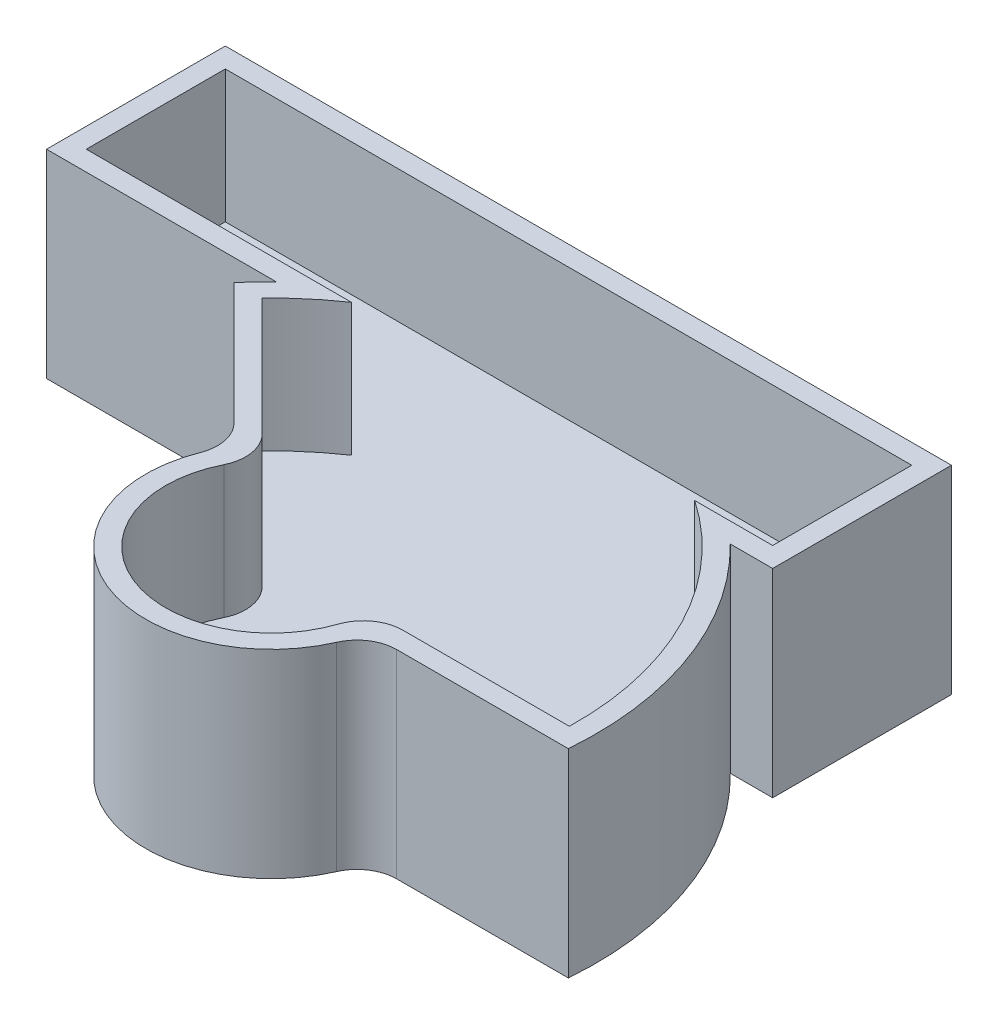
SolidWorks part; units mm, degrees
ref_plane "Alzado" through (0, 0, 0) normal (0, 0, 1) x (1, 0, 0)
ref_plane "Planta" through (0, 0, 0) normal (0, 1, 0) x (1, 0, 0)
ref_plane "Vista lateral" through (0, 0, 0) normal (1, 0, 0) x (0, 0, -1)
sketch "Croquis1" plane through (0, 0, 0) normal (0, 1, 0) x (1, 0, 0)
  line L0 (-35, 32.5) -> (35, -32.5) construction
  line L1 (-35, 32.5) -> (35, 32.5)
  line L2 (-35, 32.5) -> (-35, -32.5)
  line L3 (-35, -32.5) -> (35, -32.5)
  line L4 (35, 32.5) -> (35, -32.5)
  dimension "D1" = 70
  dimension "D2" = 65
extrude "Extruir1" add sketch "Croquis1" along normal blind 5
sketch "Croquis2" plane through (0, 5, 0) normal (0, 1, 0) x (1, 0, 0)
  line L0 (0, 32.5) -> (0, -32.5) construction
  line L1 (35, 32.5) -> (-35, 32.5) construction
  line L2 (-35, -32.5) -> (35, -32.5) construction
  circle A0 centre (0, -17.5) radius 4
  dimension "D1" = 8
  dimension "D2" = 15
extrude "Extruir2" cut sketch "Croquis2" against normal blind 5
sketch "Croquis3" plane through (0, 5, 0) normal (0, 1, 0) x (1, 0, 0)
  line L0 (0, -32.5) -> (0, 32.5) construction
  line L1 (-35, -32.5) -> (35, -32.5) construction
  line L2 (35, 32.5) -> (-35, 32.5) construction
  line L3 (-32.9868, -32.5) -> (-32.9868, 32.5) construction
  line L4 (-32.9868, 1.5) -> (-12.9615, 1.5)
  line L5 (18.8496, -32.5) -> (18.8496, 32.5) construction
  line L6 (-32.9868, 3.5) -> (18.8496, 3.5) construction
  line L7 (-32.9868, 2) -> (0, 2) construction
  line L8 (-32.9868, 11.5) -> (18.8496, 11.5) construction
  line L9 (0, -17.5) -> (-14.8492, -2.6508) construction
  line L10 (0, -17.5) -> (14.8492, -2.6508) construction
  line L11 (0, 2) -> (18.8496, 2) construction
  line L12 (-32.9868, 2) -> (18.8496, 2) construction
  line L13 (-32.9868, 12) -> (18.8496, 12)
  line L14 (-5.3033, -12.1967) -> (-16.2635, -1.2365) construction
  line L15 (12.9615, 1.5) -> (18.8496, 1.5)
  line L16 (-32.9868, 1.5) -> (18.8496, 1.5) construction
  line L17 (7.9844, -18) -> (22.9946, -18)
  line L18 (-5.9993, -12.2078) -> (-16.6132, -1.5939)
  line L19 (0, -17.5) -> (23, -17.5) construction
  line L20 (7.5, -17.5) -> (23, -17.5) construction
  line L21 (-5.6569, -12.5503) -> (-16.617, -1.5901) construction
  line L22 (7.5, -18) -> (23, -18) construction
  line L23 (-32.9868, 12) -> (-32.9868, 1.5)
  line L24 (18.8496, 12) -> (18.8496, 1.5)
  line L25 (-34.4868, 13.5) -> (20.3496, 13.5)
  line L26 (20.3496, 13.5) -> (20.3496, 0)
  line L27 (17.1464, 0) -> (20.3496, 0)
  line L28 (9.2871, -19.5) -> (24.4182, -19.5)
  line L29 (-7.9812, -12.3473) -> (-18.6805, -1.6479)
  line L30 (-34.4868, 0) -> (-17.1464, 0)
  line L31 (-34.4868, 13.5) -> (-34.4868, 0)
  circle A0 centre (0, -17.5) radius 21 construction
  circle A1 centre (0, -17.5) radius 7.5 construction
  arc A2 (-12.9615, 1.5) -> (-16.6132, -1.5939) centre (0, -17.5) ccw
  circle A3 centre (0, -17.5) radius 23 construction
  arc A4 (-5.9993, -12.2078) -> (7.9844, -18) centre (0, -17.5) ccw
  arc A5 (22.9946, -18) -> (12.9615, 1.5) centre (0, -17.5) ccw
  arc A6 (24.4182, -19.5) -> (17.1464, 0) centre (0, -17.5) ccw
  arc A7 (-7.9812, -12.3473) -> (9.2871, -19.5) centre (0, -17.5) ccw
  arc A8 (-17.1464, 0) -> (-18.6805, -1.6479) centre (0, -17.5) ccw
  dimension "D3" = 42
  dimension "D8" = 15
  dimension "D9" = 46
  dimension "D14" = 0.5
  dimension "D2" = 51.8364
  dimension "D6" = 90
  dimension "D7" = 45
  dimension "D1" = 32.9868
  dimension "D4" = 1.5
  dimension "D5" = 9.5
  dimension "D10" = 2
  dimension "D11" = 0.5
  dimension "D12" = 0.5
  dimension "D13" = 0.5
  dimension "D15" = 1.5
extrude "Extruir3" add sketch "Croquis3" along normal blind 10
sketch "Croquis4" plane through (0, 5, 0) normal (0, 1, 0) x (1, 0, 0)
  line L0 (-34.4868, 0) -> (-17.1464, 0) construction
  line L1 (-34.4868, 13.5) -> (-34.4868, 0) construction
  line L2 (20.3496, 13.5) -> (-34.4868, 13.5) construction
  line L3 (20.3496, 0) -> (20.3496, 13.5) construction
  line L4 (17.1464, 0) -> (20.3496, 0) construction
  line L5 (9.2871, -19.5) -> (24.4182, -19.5) construction
  line L6 (-18.6805, -1.6479) -> (-7.9812, -12.3473) construction
  line L7 (-34.4868, 0) -> (-17.1464, 0)
  line L8 (-34.4868, 13.5) -> (-34.4868, 0)
  line L9 (20.3496, 13.5) -> (-34.4868, 13.5)
  line L10 (20.3496, 0) -> (20.3496, 13.5)
  line L11 (17.1464, 0) -> (20.3496, 0)
  line L12 (9.2871, -19.5) -> (24.4182, -19.5)
  line L13 (-18.6805, -1.6479) -> (-7.9812, -12.3473)
  arc A0 (-17.1464, 0) -> (-18.6805, -1.6479) centre (0, -17.5) ccw construction
  arc A1 (24.4182, -19.5) -> (17.1464, 0) centre (0, -17.5) ccw construction
  arc A2 (-7.9812, -12.3473) -> (9.2871, -19.5) centre (0, -17.5) ccw construction
  arc A3 (-17.1464, 0) -> (-18.6805, -1.6479) centre (0, -17.5) ccw
  arc A4 (24.4182, -19.5) -> (17.1464, 0) centre (0, -17.5) ccw
  arc A5 (-7.9812, -12.3473) -> (9.2871, -19.5) centre (0, -17.5) ccw
extrude "Extruir4" cut sketch "Croquis4" against normal blind 10 flip side to cut
fillet "Redondeo1" radius 3 4 edges at (9.2871, 7.5, 19.5) (-7.9812, 7.5, 12.3473) (7.9844, 10, 18) (-5.9993, 10, 12.2078)
